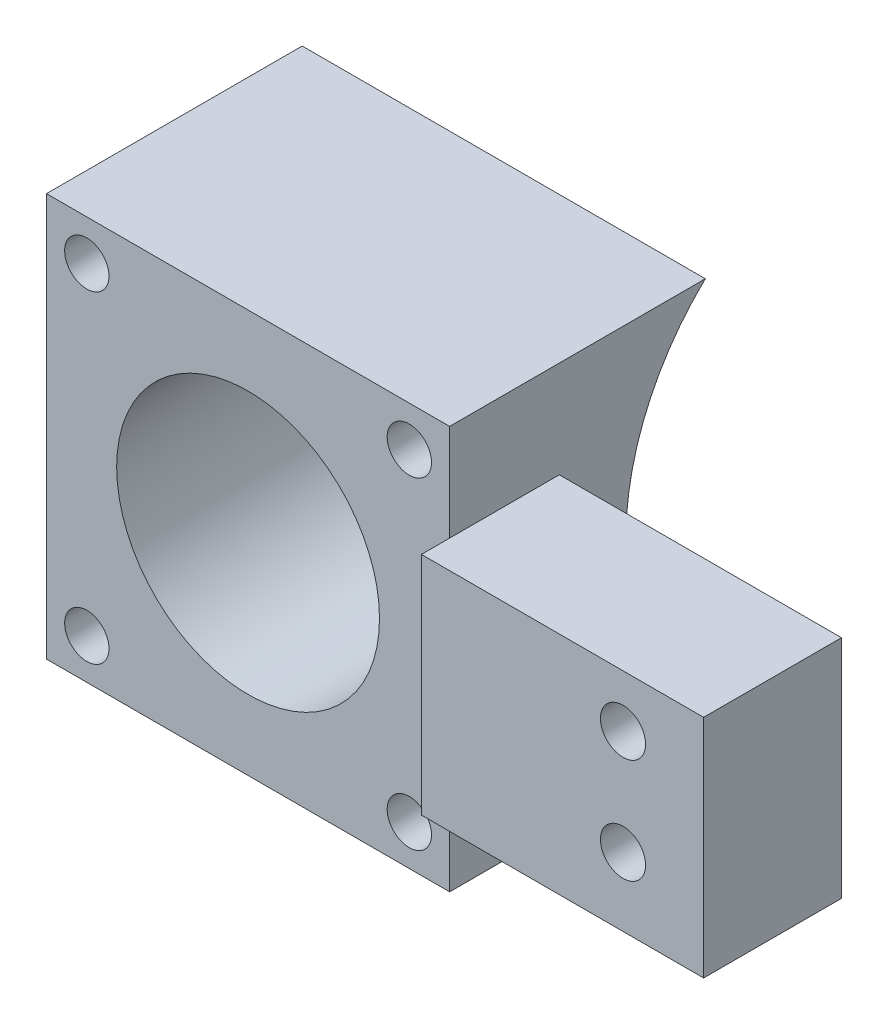
SolidWorks part; units mm, degrees
ref_plane "Front Plane" through (0, 0, 0) normal (0, 0, 1) x (1, 0, 0)
ref_plane "Top Plane" through (0, 0, 0) normal (0, 1, 0) x (1, 0, 0)
ref_plane "Right Plane" through (0, 0, 0) normal (1, 0, 0) x (0, 0, -1)
sketch "Sketch1" plane through (0, 0, 0) normal (0, 0, 1) x (1, 0, 0)
  line L1 (-25, 23) -> (25, 23)
  line L2 (-25, 23) -> (-25, -27)
  line L3 (-25, -27) -> (25, -27)
  line L4 (25, 23) -> (25, -27)
  line L5 (-25, 23) -> (25, -27) construction
  line L6 (-25, -27) -> (25, 23) construction
  circle A0 centre (0, -2) radius 16.3
  circle A1 centre (-20, 18) radius 2.75
  circle A2 centre (20, 18) radius 2.75
  circle A3 centre (20, -22) radius 2.75
  circle A4 centre (-20, -22) radius 2.75
  point P0 (0, -2)
  dimension "D4" = 32.6
  dimension "D6" = 5.5
  dimension "D1" = 2
  dimension "D2" = 50
  dimension "D3" = 50
  dimension "D5" = 20
  dimension "D7" = 20
  dimension "D9" = 20
  dimension "D10" = 20
extrude "Boss-Extrude1" add sketch "Sketch1" along normal blind 53.6
sketch "Sketch2" plane through (0, 0, 0) normal (1, 0, 0) x (0, 0, -1)
  circle A0 centre (0, 0) radius 31.75
  dimension "D1" = 63.5
extrude "Cut-Extrude1" cut sketch "Sketch2" against normal through all and the other way through all
sketch "Sketch3" plane through (-25, 0, 0) normal (-1, 0, 0) x (0, 0, 1)
  line L3 (53.6, 23) -> (21.8875, 23)
  line L4 (16.7052, -27) -> (53.6, -27)
  line L5 (53.6, -27) -> (53.6, 23)
  line L6 (53.6, 23) -> (21.8875, 23)
  line L7 (16.7052, -27) -> (53.6, -27)
  line L8 (53.6, -27) -> (53.6, 23)
  arc A1 (16.7052, -27) -> (21.8875, 23) centre (0, 0) ccw
  arc A2 (16.7052, -27) -> (21.8875, 23) centre (0, 0) ccw
  dimension "D1" = 0
sketch "Sketch4" plane through (25, 0, 0) normal (1, 0, 0) x (0, 0, -1)
  line L3 (-53.6, -27) -> (-16.7052, -27)
  line L4 (-21.8875, 23) -> (-53.6, 23)
  line L5 (-53.6, 23) -> (-53.6, -27)
  line L8 (-53.6, 11) -> (-53.6, -17)
  line L12 (-53.6, 11) -> (-29.7836, 11)
  line L13 (-53.6, 23) -> (-21.8875, 23) construction
  line L14 (0, 0) -> (-85.4701, 0) construction
  line L15 (-53.6, -11) -> (-29.7836, -11) construction
  line L16 (-53.6, -17) -> (-26.8153, -17)
  arc A0 (-21.8875, 23) -> (-16.7052, -27) centre (0, 0) ccw construction
  arc A1 (-21.8875, 23) -> (-16.7052, -27) centre (0, 0) ccw
  arc A2 (-29.7836, 11) -> (-26.8153, -17) centre (0, 0) ccw
  dimension "D3" = 12
  dimension "D4" = 6
  dimension "D1" = 0
extrude "Boss-Extrude3" add sketch "Sketch4" along normal blind 35
sketch "Sketch12" plane through (0, 0, 53.6) normal (0, 0, 1) x (1, 0, 0)
  line L6 (60, 11) -> (60, -17) construction
  line L7 (60, 11) -> (25, 11) construction
  line L8 (60, -17) -> (25, -17) construction
  line L9 (60, 11) -> (60, -17)
  line L10 (60, 11) -> (25, 11)
  line L11 (60, -17) -> (25, -17)
  line L12 (25, 11) -> (25, -17)
sketch "Sketch10" plane through (0, 0, 53.6) normal (0, 0, 1) x (1, 0, 0)
  line L0 (50, 4.5) -> (50, -8.5) construction
  line L1 (60, -2) -> (0, -2) construction
  line L2 (60, 11) -> (60, -17) construction
  line L3 (25, -27) -> (25, -17) construction
  line L4 (60, 11) -> (60, -17) construction
  line L5 (50, 22) -> (50, -27) construction
  line L6 (-25, -27) -> (25, -27) construction
  circle A0 centre (50, 4.5) radius 2.8
  circle A1 centre (50, -8.5) radius 2.8
  point P8 (50, -2)
  point P10 (60, -3)
  dimension "D1" = 5.6
  dimension "D2" = 1
  dimension "D3" = 13
  dimension "D4" = 25
extrude "Cut-Extrude6" cut sketch "Sketch10" against normal blind 10 and the other way through all
sketch "Sketch13" plane through (60, 0, 0) normal (1, 0, 0) x (0, 0, -1)
  line L0 (-29.7836, 11) -> (-40, 11)
  line L1 (-29.7836, 11) -> (-53.6, 11) construction
  line L2 (-40, 11) -> (-40, -17)
  line L3 (-53.6, -17) -> (-26.8153, -17) construction
  line L4 (-40, -17) -> (-26.8153, -17)
  arc A0 (-29.7836, 11) -> (-26.8153, -17) centre (0, 0) ccw construction
  arc A1 (-29.7836, 11) -> (-26.8153, -17) centre (0, 0) ccw
  dimension "D1" = 40
extrude "Cut-Extrude8" cut sketch "Sketch13" against normal up to surface (35 mm away) up to face at (25, 17.1131, 39.8897)
sketch "Sketch14" [suppressed] plane through (60, 0, 0) normal (1, 0, 0) x (0, 0, -1)
  line L0 (-33.6, 11) -> (-33.6, -17) construction
  line L1 (-45.6, -17) -> (-33.6, -17) construction
  line L2 (-45.6, -17) -> (-45.6, 11) construction
  line L3 (-33.6, 11) -> (-45.6, 11) construction
  line L4 (-33.6, 11) -> (-33.6, -17)
  line L5 (-45.6, -17) -> (-33.6, -17)
  line L6 (-45.6, -17) -> (-45.6, 11) construction
  line L7 (-33.6, 11) -> (-45.6, 11)
  line L8 (-33.6, -3) -> (-36.6, -3) construction
  line L9 (-36.6, -3) -> (-36.6, 11) construction
  line L10 (-36.6, -3) -> (-36.6, -17) construction
  line L11 (-36.6, 4) -> (-36.6, -10)
  arc A0 (-45.6, 11) -> (-36.6, 4) centre (-45.6, 1.7143) cw
  arc A1 (-45.6, -17) -> (-36.6, -10) centre (-45.6, -7.7143) ccw
  dimension "D1" = 3
extrude "Cut-Extrude9" [suppressed] cut sketch "Sketch14" against normal up to surface (35 mm away) up to face at (25, -2.6592, 43.1596)
sketch "Sketch16" plane through (0, 0, 53.6) normal (0, 0, 1) x (1, 0, 0)
  line L0 (60, 11) -> (60, -17) construction
  line L1 (60, -17) -> (25, -17) construction
  line L2 (60, 11) -> (25, 11) construction
  line L3 (25, 11) -> (25, -17) construction
  line L4 (60, 11) -> (60, -17)
  line L5 (60, -17) -> (25, -17)
  line L6 (60, 11) -> (25, 11)
  line L7 (25, 11) -> (25, -17)
  circle A0 centre (50, 4.5) radius 2.8 construction
  circle A1 centre (50, -8.5) radius 2.8 construction
  circle A2 centre (50, 4.5) radius 2.8
  circle A3 centre (50, -8.5) radius 2.8
extrude "Boss-Extrude4" add sketch "Sketch16" along normal blind 3.5
